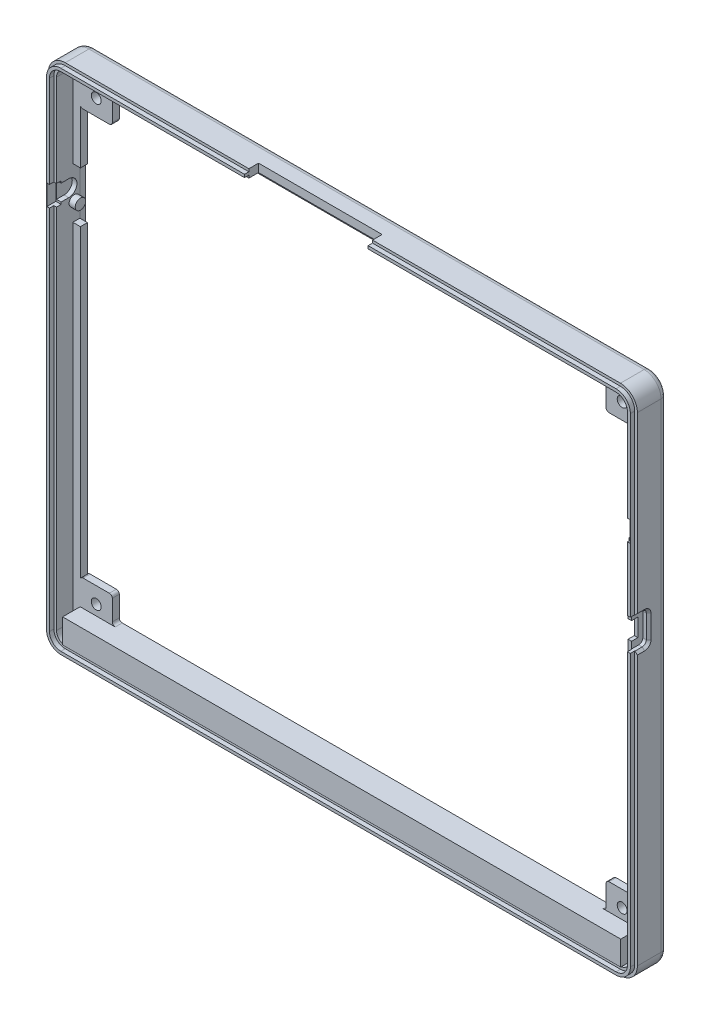
SolidWorks part; units mm, degrees
ref_plane "Спереди" through (0, 0, 0) normal (0, 0, 1) x (1, 0, 0)
ref_plane "Сверху" through (0, 0, 0) normal (0, 1, 0) x (1, 0, 0)
ref_plane "Справа" through (0, 0, 0) normal (1, 0, 0) x (0, 0, -1)
other "Configuration Table"
sketch "Perimeter_shell_profile" plane through (0, 0, 0) normal (0, 0, 1) x (1, 0, 0)
  line L0 (0, -9.8) -> (190, -9.8)
  line L1 (195.8, -4) -> (195.8, 160)
  line L2 (190, 165.8) -> (0, 165.8)
  line L3 (-5.8, 160) -> (-5.8, -4)
  line L4 (0, -7) -> (190, -7)
  line L5 (193, -4) -> (193, 160)
  line L6 (190, 163) -> (0, 163)
  line L7 (-3, 160) -> (-3, -4)
  arc A0 (190, -9.8) -> (195.8, -4) centre (190, -4) ccw
  arc A1 (195.8, 160) -> (190, 165.8) centre (190, 160) ccw
  arc A2 (0, 165.8) -> (-5.8, 160) centre (0, 160) ccw
  arc A3 (-5.8, -4) -> (0, -9.8) centre (0, -4) ccw
  arc A4 (190, -7) -> (193, -4) centre (190, -4) ccw
  arc A5 (193, 160) -> (190, 163) centre (190, 160) ccw
  arc A6 (0, 163) -> (-3, 160) centre (0, 160) ccw
  arc A7 (-3, -4) -> (0, -7) centre (0, -4) ccw
extrude "Perimeter_shell" add sketch "Perimeter_shell_profile" along normal blind 5.6 from offset 7.6 offset against normal yes
sketch "Open_back_frame_profile" plane through (0, 0, 0) normal (0, 0, 1) x (1, 0, 0)
  line L0 (0, -9.8) -> (190, -9.8)
  line L1 (195.8, -4) -> (195.8, 160)
  line L2 (190, 165.8) -> (0, 165.8)
  line L3 (-5.8, 160) -> (-5.8, -4)
  line L4 (1.6, -4.4) -> (188.4, -4.4)
  line L5 (190.4, -2.4) -> (190.4, 158.4)
  line L6 (188.4, 160.4) -> (1.6, 160.4)
  line L7 (-0.4, 158.4) -> (-0.4, -2.4)
  arc A0 (190, -9.8) -> (195.8, -4) centre (190, -4) ccw
  arc A1 (195.8, 160) -> (190, 165.8) centre (190, 160) ccw
  arc A2 (0, 165.8) -> (-5.8, 160) centre (0, 160) ccw
  arc A3 (-5.8, -4) -> (0, -9.8) centre (0, -4) ccw
  arc A4 (188.4, -4.4) -> (190.4, -2.4) centre (188.4, -2.4) ccw
  arc A5 (190.4, 158.4) -> (188.4, 160.4) centre (188.4, 158.4) ccw
  arc A6 (1.6, 160.4) -> (-0.4, 158.4) centre (1.6, 158.4) ccw
  arc A7 (-0.4, -2.4) -> (1.6, -4.4) centre (1.6, -2.4) ccw
extrude "Open_back_frame" add sketch "Open_back_frame_profile" along normal blind 4.5 from offset 12.1 offset against normal yes
sketch "PCB_mount_web_0_profile" plane through (0, 0, 0) normal (0, 0, 1) x (1, 0, 0)
  line L0 (0.5, -6) -> (9.5, -6)
  line L1 (10.5, -5) -> (10.5, 9.5)
  line L2 (9.5, 10.5) -> (0.5, 10.5)
  line L3 (-0.5, 9.5) -> (-0.5, -5)
  arc A0 (9.5, -6) -> (10.5, -5) centre (9.5, -5) ccw
  arc A1 (10.5, 9.5) -> (9.5, 10.5) centre (9.5, 9.5) ccw
  arc A2 (0.5, 10.5) -> (-0.5, 9.5) centre (0.5, 9.5) ccw
  arc A3 (-0.5, -5) -> (0.5, -6) centre (0.5, -5) ccw
extrude "PCB_mount_web_0" add sketch "PCB_mount_web_0_profile" along normal blind 4.5 from offset 12.1 offset against normal yes
sketch "PCB_M3_through_0_profile" plane through (0, 0, 0) normal (0, 0, 1) x (1, 0, 0)
  circle A0 centre (5, 5) radius 1.7
extrude "PCB_M3_through_0" cut sketch "PCB_M3_through_0_profile" against normal blind 4.7 from offset 7.5 offset against normal yes
sketch "PCB_mount_web_1_profile" plane through (0, 0, 0) normal (0, 0, 1) x (1, 0, 0)
  line L0 (180.5, -6) -> (189.5, -6)
  line L1 (190.5, -5) -> (190.5, 9.5)
  line L2 (189.5, 10.5) -> (180.5, 10.5)
  line L3 (179.5, 9.5) -> (179.5, -5)
  arc A0 (189.5, -6) -> (190.5, -5) centre (189.5, -5) ccw
  arc A1 (190.5, 9.5) -> (189.5, 10.5) centre (189.5, 9.5) ccw
  arc A2 (180.5, 10.5) -> (179.5, 9.5) centre (180.5, 9.5) ccw
  arc A3 (179.5, -5) -> (180.5, -6) centre (180.5, -5) ccw
extrude "PCB_mount_web_1" add sketch "PCB_mount_web_1_profile" along normal blind 4.5 from offset 12.1 offset against normal yes
sketch "PCB_M3_through_1_profile" plane through (0, 0, 0) normal (0, 0, 1) x (1, 0, 0)
  circle A0 centre (185, 5) radius 1.7
extrude "PCB_M3_through_1" cut sketch "PCB_M3_through_1_profile" against normal blind 4.7 from offset 7.5 offset against normal yes
sketch "PCB_mount_web_2_profile" plane through (0, 0, 0) normal (0, 0, 1) x (1, 0, 0)
  line L0 (0.5, 149.5) -> (9.5, 149.5)
  line L1 (10.5, 150.5) -> (10.5, 161)
  line L2 (9.5, 162) -> (0.5, 162)
  line L3 (-0.5, 161) -> (-0.5, 150.5)
  arc A0 (9.5, 149.5) -> (10.5, 150.5) centre (9.5, 150.5) ccw
  arc A1 (10.5, 161) -> (9.5, 162) centre (9.5, 161) ccw
  arc A2 (0.5, 162) -> (-0.5, 161) centre (0.5, 161) ccw
  arc A3 (-0.5, 150.5) -> (0.5, 149.5) centre (0.5, 150.5) ccw
extrude "PCB_mount_web_2" add sketch "PCB_mount_web_2_profile" along normal blind 4.5 from offset 12.1 offset against normal yes
sketch "PCB_M3_through_2_profile" plane through (0, 0, 0) normal (0, 0, 1) x (1, 0, 0)
  circle A0 centre (5, 155) radius 1.7
extrude "PCB_M3_through_2" cut sketch "PCB_M3_through_2_profile" against normal blind 4.7 from offset 7.5 offset against normal yes
sketch "PCB_mount_web_3_profile" plane through (0, 0, 0) normal (0, 0, 1) x (1, 0, 0)
  line L0 (180.5, 149.5) -> (189.5, 149.5)
  line L1 (190.5, 150.5) -> (190.5, 161)
  line L2 (189.5, 162) -> (180.5, 162)
  line L3 (179.5, 161) -> (179.5, 150.5)
  arc A0 (189.5, 149.5) -> (190.5, 150.5) centre (189.5, 150.5) ccw
  arc A1 (190.5, 161) -> (189.5, 162) centre (189.5, 161) ccw
  arc A2 (180.5, 162) -> (179.5, 161) centre (180.5, 161) ccw
  arc A3 (179.5, 150.5) -> (180.5, 149.5) centre (180.5, 150.5) ccw
extrude "PCB_mount_web_3" add sketch "PCB_mount_web_3_profile" along normal blind 4.5 from offset 12.1 offset against normal yes
sketch "PCB_M3_through_3_profile" plane through (0, 0, 0) normal (0, 0, 1) x (1, 0, 0)
  circle A0 centre (185, 155) radius 1.7
extrude "PCB_M3_through_3" cut sketch "PCB_M3_through_3_profile" against normal blind 4.7 from offset 7.5 offset against normal yes
sketch "Rear_glass_seat_profile" plane through (0, 0, 0) normal (0, 0, 1) x (1, 0, 0)
  line L0 (0, -7.25) -> (190, -7.25)
  line L1 (193.25, -4) -> (193.25, 160)
  line L2 (190, 163.25) -> (0, 163.25)
  line L3 (-3.25, 160) -> (-3.25, -4)
  arc A0 (190, -7.25) -> (193.25, -4) centre (190, -4) ccw
  arc A1 (193.25, 160) -> (190, 163.25) centre (190, 160) ccw
  arc A2 (0, 163.25) -> (-3.25, 160) centre (0, 160) ccw
  arc A3 (-3.25, -4) -> (0, -7.25) centre (0, -4) ccw
extrude "Rear_glass_seat" cut sketch "Rear_glass_seat_profile" against normal blind 2.2 from offset 10 offset against normal yes
sketch "PCB_lower_edge_web_profile" plane through (0, 0, 0) normal (0, 0, 1) x (1, 0, 0)
  line L0 (-0.5, -6.8) -> (190.5, -6.8)
  line L1 (190.5, -6.8) -> (190.5, 1.5)
  line L2 (190.5, 1.5) -> (-0.5, 1.5)
  line L3 (-0.5, 1.5) -> (-0.5, -6.8)
extrude "PCB_lower_edge_web" add sketch "PCB_lower_edge_web_profile" along normal blind 8.4 from offset 10 offset against normal yes
fillet "PCB_support_root_round" radius 1 2 edges at (179.5, 1.5, -8.8) (10.5, 1.5, -8.8)
sketch "Locating_tongue_profile" plane through (0, 0, 0) normal (0, 0, 1) x (1, 0, 0)
  line L0 (0, -8.9) -> (190, -8.9)
  line L1 (194.9, -4) -> (194.9, 160)
  line L2 (190, 164.9) -> (0, 164.9)
  line L3 (-4.9, 160) -> (-4.9, -4)
  line L4 (0, -7.9) -> (190, -7.9)
  line L5 (193.9, -4) -> (193.9, 160)
  line L6 (190, 163.9) -> (0, 163.9)
  line L7 (-3.9, 160) -> (-3.9, -4)
  arc A0 (190, -8.9) -> (194.9, -4) centre (190, -4) ccw
  arc A1 (194.9, 160) -> (190, 164.9) centre (190, 160) ccw
  arc A2 (0, 164.9) -> (-4.9, 160) centre (0, 160) ccw
  arc A3 (-4.9, -4) -> (0, -8.9) centre (0, -4) ccw
  arc A4 (190, -7.9) -> (193.9, -4) centre (190, -4) ccw
  arc A5 (193.9, 160) -> (190, 163.9) centre (190, 160) ccw
  arc A6 (0, 163.9) -> (-3.9, 160) centre (0, 160) ccw
  arc A7 (-3.9, -4) -> (0, -7.9) centre (0, -4) ccw
extrude "Locating_tongue" add sketch "Locating_tongue_profile" along normal blind 1.5 from offset 2 offset against normal yes
sketch "Top_connector_access_profile" plane through (0, 0, 0) normal (0, 0, 1) x (1, 0, 0)
  line L0 (62.8501, 153.5) -> (105.1501, 153.5)
  line L1 (105.1501, 153.5) -> (105.1501, 166.8)
  line L2 (105.1501, 166.8) -> (62.8501, 166.8)
  line L3 (62.8501, 166.8) -> (62.8501, 153.5)
extrude "Top_connector_access" cut sketch "Top_connector_access_profile" against normal blind 19.6 from offset 14.3
sketch "Power_retaining_web_profile" plane through (0, 0, 0) normal (0, 0, 1) x (1, 0, 0)
  line L0 (192.6, 87.5) -> (193.2, 87.5)
  line L1 (193.2, 87.5) -> (193.2, 101)
  line L2 (193.2, 101) -> (192.6, 101)
  line L3 (192.6, 101) -> (192.6, 87.5)
extrude "Power_retaining_web" add sketch "Power_retaining_web_profile" along normal blind 3.85 from offset 5.85 offset against normal yes
sketch "Slider_slot_profile" plane through (0, 0, 0) normal (0, 0, 1) x (1, 0, 0)
  line L0 (189.2, 91.22) -> (197, 91.22)
  line L1 (197, 91.22) -> (197, 97.32)
  line L2 (197, 97.32) -> (189.2, 97.32)
  line L3 (189.2, 97.32) -> (189.2, 91.22)
extrude "Slider_slot" cut sketch "Slider_slot_profile" against normal blind 3.8 from offset 0.35 offset against normal yes
sketch "Power_thumb_recess_profile" plane through (0, 0, 0) normal (1, 0, 0) x (0, 0, -1)
  line L0 (5.85, 90.32) -> (5.85, 98.22)
  line L1 (4.45, 99.62) -> (0.05, 99.62)
  line L2 (-1.35, 98.22) -> (-1.35, 90.32)
  line L3 (0.05, 88.92) -> (4.45, 88.92)
  arc A0 (5.85, 98.22) -> (4.45, 99.62) centre (4.45, 98.22) ccw
  arc A1 (0.05, 99.62) -> (-1.35, 98.22) centre (0.05, 98.22) ccw
  arc A2 (-1.35, 90.32) -> (0.05, 88.92) centre (0.05, 90.32) ccw
  arc A3 (4.45, 88.92) -> (5.85, 90.32) centre (4.45, 90.32) ccw
extrude "Power_thumb_recess" cut sketch "Power_thumb_recess_profile" along normal blind 3.4 from offset 193.8
ref_plane "Power_recess_bevel_plane_0" through (195, 0, 0) normal (1, 0, 0) x (0, 0, -1)
sketch "Power_recess_bevel_section_0" plane through (195, 0, 0) normal (1, 0, 0) x (0, 0, -1)
  line L0 (5.85, 90.32) -> (5.85, 98.22)
  line L1 (4.45, 99.62) -> (0.05, 99.62)
  line L2 (-1.35, 98.22) -> (-1.35, 90.32)
  line L3 (0.05, 88.92) -> (4.45, 88.92)
  arc A0 (5.85, 98.22) -> (4.45, 99.62) centre (4.45, 98.22) ccw
  arc A1 (0.05, 99.62) -> (-1.35, 98.22) centre (0.05, 98.22) ccw
  arc A2 (-1.35, 90.32) -> (0.05, 88.92) centre (0.05, 90.32) ccw
  arc A3 (4.45, 88.92) -> (5.85, 90.32) centre (4.45, 90.32) ccw
ref_plane "Power_recess_bevel_plane_1" through (195.8, 0, 0) normal (1, 0, 0) x (0, 0, -1)
sketch "Power_recess_bevel_section_1" plane through (195.8, 0, 0) normal (1, 0, 0) x (0, 0, -1)
  line L0 (6.65, 90.32) -> (6.65, 98.22)
  line L1 (4.45, 100.42) -> (0.05, 100.42)
  line L2 (-2.15, 98.22) -> (-2.15, 90.32)
  line L3 (0.05, 88.12) -> (4.45, 88.12)
  arc A0 (6.65, 98.22) -> (4.45, 100.42) centre (4.45, 98.22) ccw
  arc A1 (0.05, 100.42) -> (-2.15, 98.22) centre (0.05, 98.22) ccw
  arc A2 (-2.15, 90.32) -> (0.05, 88.12) centre (0.05, 90.32) ccw
  arc A3 (4.45, 88.12) -> (6.65, 90.32) centre (4.45, 90.32) ccw
loft "Power_recess_bevel" cut profiles "Power_recess_bevel_section_0", "Power_recess_bevel_section_1"
sketch "Internal_hinge_clearance_0_profile" plane through (0, 0, 0) normal (0, 0, 1) x (1, 0, 0)
  line L0 (-3, 114.2) -> (4.2, 114.2)
  line L1 (4.2, 114.2) -> (4.2, 131.6)
  line L2 (4.2, 131.6) -> (-3, 131.6)
  line L3 (-3, 131.6) -> (-3, 114.2)
extrude "Internal_hinge_clearance_0" cut sketch "Internal_hinge_clearance_0_profile" against normal blind 10.3 from offset 1.9 offset against normal yes
sketch "Internal_stop_pin_0_profile" plane through (0, 0, 0) normal (1, 0, 0) x (0, 0, -1)
  circle A0 centre (8.1134, 120.3806) radius 1.8
extrude "Internal_stop_pin_0" add sketch "Internal_stop_pin_0_profile" along normal blind 2.6 from offset 3.5 offset against normal yes
sketch "Blind_axle_bearing_0_profile" plane through (0, 0, 0) normal (1, 0, 0) x (0, 0, -1)
  circle A0 centre (6.2, 125) radius 2.8
extrude "Blind_axle_bearing_0" cut sketch "Blind_axle_bearing_0_profile" along normal blind 1.7 from offset 4.6 offset against normal yes
sketch "Axle_assembly_entry_0_profile" plane through (0, 0, 0) normal (1, 0, 0) x (0, 0, -1)
  line L0 (6.2, 122.2) -> (6.2, 127.8)
  line L1 (6.2, 127.8) -> (-0.1, 127.8)
  line L2 (-0.1, 127.8) -> (-0.1, 122.2)
  line L3 (-0.1, 122.2) -> (6.2, 122.2)
extrude "Axle_assembly_entry_0" cut sketch "Axle_assembly_entry_0_profile" along normal blind 1.7 from offset 4.6 offset against normal yes
sketch "Keeper_seat_0_profile" plane through (0, 0, 0) normal (0, 0, 1) x (1, 0, 0)
  line L0 (-4.8, 121.5) -> (-2.7, 121.5)
  line L1 (-2.7, 121.5) -> (-2.7, 128.5)
  line L2 (-2.7, 128.5) -> (-4.8, 128.5)
  line L3 (-4.8, 128.5) -> (-4.8, 121.5)
extrude "Keeper_seat_0" cut sketch "Keeper_seat_0_profile" against normal blind 3.7 from offset 0.1
sketch "Internal_hinge_clearance_1_profile" plane through (0, 0, 0) normal (0, 0, 1) x (1, 0, 0)
  line L0 (185.8, 114.2) -> (193, 114.2)
  line L1 (193, 114.2) -> (193, 131.6)
  line L2 (193, 131.6) -> (185.8, 131.6)
  line L3 (185.8, 131.6) -> (185.8, 114.2)
extrude "Internal_hinge_clearance_1" cut sketch "Internal_hinge_clearance_1_profile" against normal blind 10.3 from offset 1.9 offset against normal yes
sketch "Internal_stop_pin_1_profile" plane through (0, 0, 0) normal (1, 0, 0) x (0, 0, -1)
  circle A0 centre (8.1134, 120.3806) radius 1.8
extrude "Internal_stop_pin_1" add sketch "Internal_stop_pin_1_profile" along normal blind 2.6 from offset 190.9
sketch "Blind_axle_bearing_1_profile" plane through (0, 0, 0) normal (1, 0, 0) x (0, 0, -1)
  circle A0 centre (6.2, 125) radius 2.8
extrude "Blind_axle_bearing_1" cut sketch "Blind_axle_bearing_1_profile" along normal blind 1.7 from offset 192.9
sketch "Axle_assembly_entry_1_profile" plane through (0, 0, 0) normal (1, 0, 0) x (0, 0, -1)
  line L0 (6.2, 122.2) -> (6.2, 127.8)
  line L1 (6.2, 127.8) -> (-0.1, 127.8)
  line L2 (-0.1, 127.8) -> (-0.1, 122.2)
  line L3 (-0.1, 122.2) -> (6.2, 122.2)
extrude "Axle_assembly_entry_1" cut sketch "Axle_assembly_entry_1_profile" along normal blind 1.7 from offset 192.9
sketch "Keeper_seat_1_profile" plane through (0, 0, 0) normal (0, 0, 1) x (1, 0, 0)
  line L0 (192.7, 121.5) -> (194.8, 121.5)
  line L1 (194.8, 121.5) -> (194.8, 128.5)
  line L2 (194.8, 128.5) -> (192.7, 128.5)
  line L3 (192.7, 128.5) -> (192.7, 121.5)
extrude "Keeper_seat_1" cut sketch "Keeper_seat_1_profile" against normal blind 3.7 from offset 0.1
fillet "Outer_rear_round" radius 2 8 edges at (-4.1012, -8.1012, -12.1) (95, -9.8, -12.1) (194.1012, -8.1012, -12.1) (195.8, 78, -12.1) (194.1012, 164.1012, -12.1) (95, 165.8, -12.1) (-4.1012, 164.1012, -12.1) (-5.8, 78, -12.1)
